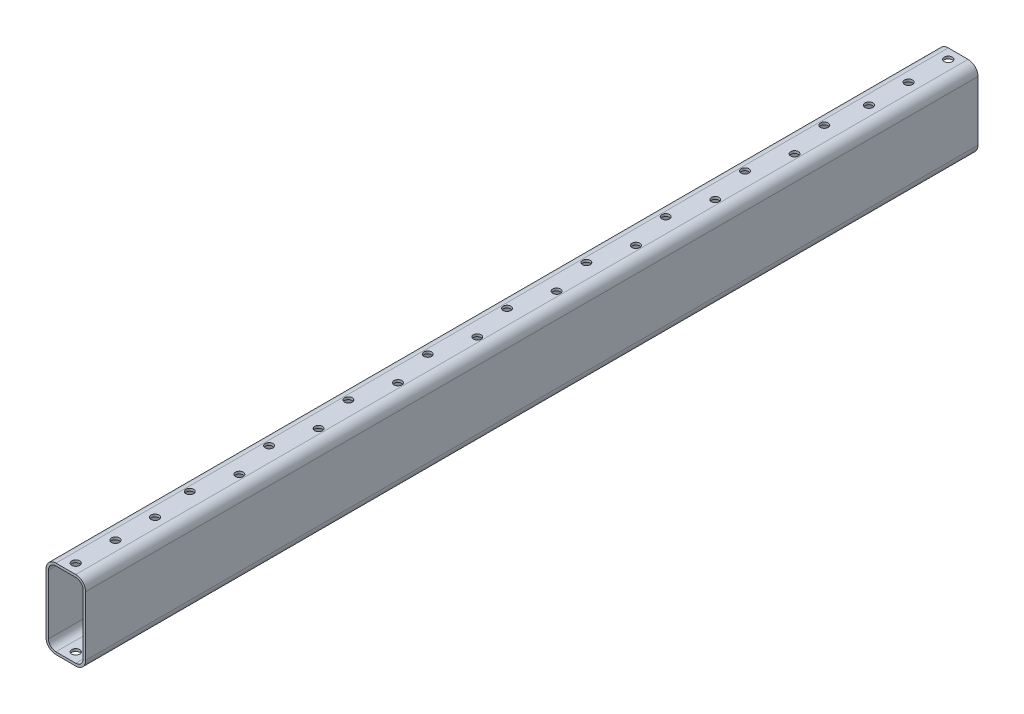
SolidWorks part; units mm, degrees
material "6061-T6 (SS)"
ref_plane "Front Plane" through (0, 0, 0) normal (0, 0, 1) x (1, 0, 0)
ref_plane "Top Plane" through (0, 0, 0) normal (0, 1, 0) x (1, 0, 0)
ref_plane "Right Plane" through (0, 0, 0) normal (1, 0, 0) x (0, 0, -1)
sketch "Sketch1" plane through (0, 0, 0) normal (0, 0, 1) x (1, 0, 0)
  line L1 (-6.35, -25.4) -> (6.35, -25.4)
  line L2 (-12.7, -19.05) -> (-12.7, 19.05)
  line L3 (-6.35, 25.4) -> (6.35, 25.4)
  line L4 (12.7, -19.05) -> (12.7, 19.05)
  line L5 (-12.7, -25.4) -> (12.7, 25.4) construction
  line L6 (-12.7, 25.4) -> (12.7, -25.4) construction
  arc A0 (-12.7, -19.05) -> (-6.35, -25.4) centre (-6.35, -19.05) ccw
  arc A1 (6.35, -25.4) -> (12.7, -19.05) centre (6.35, -19.05) ccw
  arc A2 (6.35, 25.4) -> (12.7, 19.05) centre (6.35, 19.05) cw
  arc A3 (-12.7, 19.05) -> (-6.35, 25.4) centre (-6.35, 19.05) cw
  point P0 (0, 0)
  dimension "D3" = 6.35
  dimension "D1" = 50.8
  dimension "D2" = 25.4
extrude "Extrude-Thin1" add sketch "Sketch1" along normal blind 571.5 thin thin type one direction reverse wall 1.5875
hole_wizard "#10 Clearance Hole1" positions "3DSketch1" profile "Sketch3" hole size "#10" standard "ANSI Inch" end condition through all
sketch3d "3DSketch1"
  line L1 (6.35, 25.4, 0) -> (-6.35, 25.4, 0) construction
  line L6 (0, 25.4, 571.5) -> (0, 25.4, 0) construction
  line L7 (6.35, 25.4, 571.5) -> (-6.35, 25.4, 571.5) construction
  point P57 (0, 25.4, 6.35)
  point P59 (0, 25.4, 31.75)
  point P61 (0, 25.4, 57.15)
  point P63 (0, 25.4, 539.75)
  point P65 (0, 25.4, 514.35)
  point P67 (0, 25.4, 565.15)
  dimension "D1" = 25.4
  dimension "D2" = 25.4
  dimension "D3" = 6.35
  dimension "D4" = 25.4
  dimension "D5" = 25.4
  dimension "D6" = 6.35
sketch "Sketch3" plane through (0, 25.4, 565.15) normal (1, 0, 0) x (0, 0, 1)
  line L0 (0, 0) -> (0, 50.8)
  line L1 (0, 50.8) -> (2.5527, 50.8)
  line L2 (2.5527, 50.8) -> (2.5527, 0)
  line L5 (2.5527, 0) -> (0, 0)
  line L11 (0, -6.35) -> (0, 107.95) construction
  dimension "Thru Hole Dia." = 5.1054
  dimension "Thru Hole Depth" = 50.8
hole_wizard "3/16 (0.195) Diameter Hole1" positions "Sketch4" profile "Sketch5" hole size "3/16" standard "ANSI Inch" end condition up to next
sketch "Sketch4" plane through (0, 25.4, 0) normal (0, 1, 0) x (1, 0, 0)
  point P145 (-3.1807, -82.55)
  point P148 (3.1693, -107.95)
  point P151 (-3.1807, -133.35)
  point P154 (3.1693, -158.75)
  point P157 (-3.1807, -184.15)
  point P160 (3.1693, -209.55)
  point P163 (-3.1807, -234.95)
  point P166 (3.1693, -260.35)
  point P169 (-3.1807, -285.75)
  point P172 (3.1693, -311.15)
  point P175 (-3.1807, -336.55)
  point P178 (3.1693, -361.95)
  point P181 (-3.1807, -387.35)
  point P184 (3.1693, -412.75)
  point P187 (-3.1807, -438.15)
  point P190 (3.1693, -463.55)
  point P193 (-3.1807, -488.95)
sketch "Sketch5" plane through (-3.1807, 25.4, 82.55) normal (1, 0, 0) x (0, 0, 1)
  line L0 (0, 0) -> (0, 1.5875)
  line L1 (0, 1.5875) -> (2.4765, 1.5875)
  line L2 (2.4765, 1.5875) -> (2.4765, 0)
  line L5 (2.4765, 0) -> (0, 0)
  line L11 (0, -6.35) -> (0, 107.95) construction
  dimension "Thru Hole Dia." = 4.953
  dimension "Thru Hole Depth" = 1.5875
